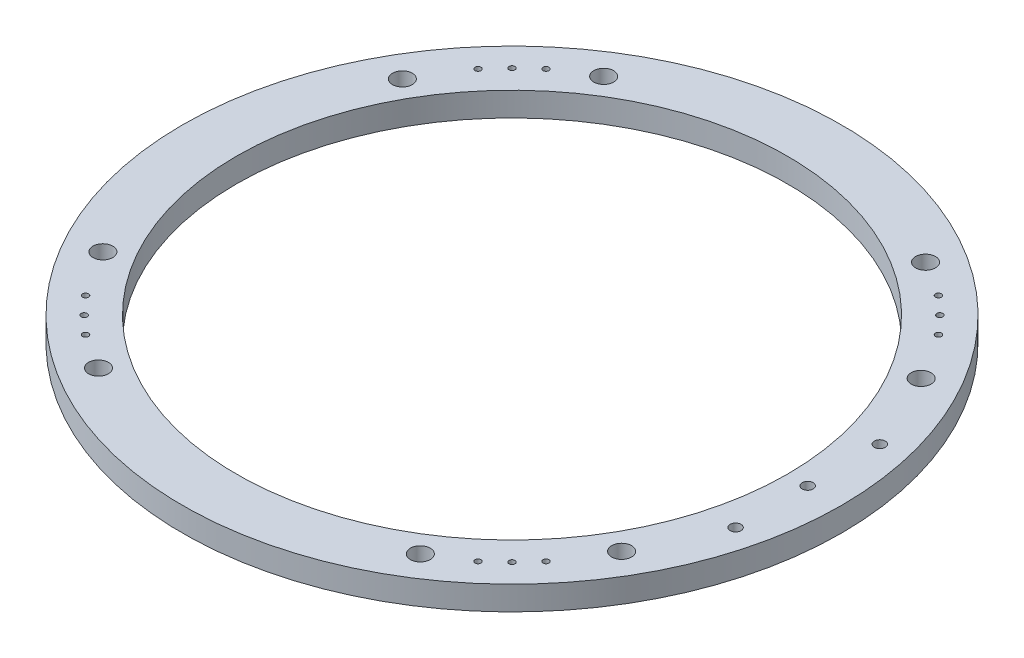
SolidWorks part; units mm, degrees
material "Oak"
ref_plane "Front Plane" through (0, 0, 0) normal (0, 0, 1) x (1, 0, 0)
ref_plane "Top Plane" through (0, 0, 0) normal (0, 1, 0) x (1, 0, 0)
ref_plane "Right Plane" through (0, 0, 0) normal (1, 0, 0) x (0, 0, -1)
sketch "Sketch1" plane through (0, 0, 0) normal (0, 0, 1) x (1, 0, 0)
  line L0 (0, 1125.8152) -> (0, -48874.1848) construction
  line L1 (145.5262, 1052.195) -> (152.4, 1052.195)
  line L9 (145.5262, 1064.895) -> (174.1012, 1064.895)
  line L10 (145.5262, 1064.895) -> (145.5262, 1052.195)
  line L11 (145.5262, 1052.195) -> (174.1012, 1052.195)
  line L12 (174.1012, 1064.895) -> (174.1012, 1052.195)
revolve "Revolve1" add sketch "Sketch1" angle 360 about L0 region at (159.8137, 1058.545, 0)
hole_wizard "9/32 (0.28125) Diameter Hole1" positions "Sketch9" profile "Sketch10" hole size "9/32" standard "ANSI Inch" end condition through all
sketch "Sketch9" plane through (0, 1052.195, 0) normal (0, -1, 0) x (-1, 0, 0)
  line L0 (0, 0) -> (113.0054, 113.0054) construction
  line L3 (0, 0) -> (103.6677, 121.6282) construction
  arc A0 (103.6677, 121.6282) -> (121.6282, 103.6677) centre (0, 0) cw
  circle A1 centre (0, 0) radius 159.8137 construction
  point P0 (103.6677, 121.6282)
  point P2 (121.6282, 103.6677)
  point P15 (113.0054, 113.0054)
sketch "Sketch10" plane through (-103.6677, 1052.195, -121.6282) normal (1, 0, 0) x (0, 0, -1)
  line L0 (0, 0) -> (0, 12.7)
  line L1 (0, 12.7) -> (3.5719, 12.7)
  line L2 (3.5719, 12.7) -> (3.5719, 0)
  line L5 (3.5719, 0) -> (0, 0)
  line L11 (0, -6.35) -> (0, 107.95) construction
  dimension "Thru Hole Dia." = 7.1437
  dimension "Thru Hole Depth" = 12.7
pattern_circular "CirPattern1" count 4 over 360 about axis through (0, 1125.8152, 0) along (0, 1, 0) of "9/32 (0.28125) Diameter Hole1"
ref_plane "Plane1" through (0, 1058.545, 0) normal (0, 1, 0) x (1, 0, 0)
hole_wizard "M5 Clearance Hole1" positions "Sketch14" profile "Sketch15" hole size "M5" standard "ANSI Metric" end condition through all
sketch "Sketch14" plane through (0, 1064.895, 0) normal (0, 1, 0) x (1, 0, 0)
  point P9 (156.21, -38.1)
  point P12 (156.21, 0)
  point P14 (156.21, 38.1)
sketch "Sketch15" plane through (156.21, 1064.895, 38.1) normal (1, 0, 0) x (0, 0, 1)
  line L0 (0, 0) -> (0, 12.7)
  line L1 (0, 12.7) -> (2.9, 12.7)
  line L2 (2.9, 12.7) -> (2.9, 0)
  line L5 (2.9, 0) -> (0, 0)
  line L11 (0, -6.35) -> (0, 107.95) construction
  dimension "Thru Hole Dia." = 5.8
  dimension "Thru Hole Depth" = 12.7
hole_wizard "Z (0.413) Diameter Hole1" positions "Sketch16" profile "Sketch17" hole size "Z" standard "ANSI Inch" end condition through all
sketch "Sketch16" plane through (0, 1064.895, 0) normal (0, 1, 0) x (1, 0, 0)
  line L0 (-137.0279, -79.1131) -> (137.0279, 79.1131) construction
  line L4 (137.0279, -79.1131) -> (-137.0279, 79.1131) construction
  line L6 (0, 0) -> (0, 158.2262) construction
  line L8 (-85.0149, -133.4467) -> (85.0149, 133.4467) construction
  line L11 (-85.0149, 133.4467) -> (85.0149, -133.4467) construction
  circle A0 centre (0, 0) radius 158.2262 construction
  circle A1 centre (0, 0) radius 145.5262 construction
  point P0 (-137.0279, -79.1131)
  point P2 (137.0279, -79.1131)
  point P4 (137.0279, 79.1131)
  point P6 (-137.0279, 79.1131)
  point P37 (-85.0149, 133.4467)
  point P39 (85.0149, 133.4467)
  point P41 (85.0149, -133.4467)
  point P43 (-85.0149, -133.4467)
  dimension "D2" = 12.7
  dimension "D1" = 120
  dimension "D3" = 65
sketch "Sketch17" plane through (-137.0279, 1064.895, 79.1131) normal (1, 0, 0) x (0, 0, 1)
  line L0 (0, 0) -> (0, 12.7)
  line L1 (0, 12.7) -> (5.2451, 12.7)
  line L2 (5.2451, 12.7) -> (5.2451, 0)
  line L5 (5.2451, 0) -> (0, 0)
  line L11 (0, -6.35) -> (0, 107.95) construction
  dimension "Thru Hole Dia." = 10.4902
  dimension "Thru Hole Depth" = 12.7
sketch "Sketch18" plane through (0, 1064.895, 0) normal (0, 1, 0) x (1, 0, 0)
  circle A5 centre (-103.6677, 121.6282) radius 1.5875
  circle A6 centre (-113.0054, 113.0054) radius 1.5875
  circle A7 centre (-121.6282, 103.6677) radius 1.5875
  circle A10 centre (103.6677, 121.6282) radius 1.5875
  circle A11 centre (113.0054, 113.0054) radius 1.5875
  circle A12 centre (121.6282, 103.6677) radius 1.5875
  circle A14 centre (-121.6282, -103.6677) radius 1.5875
  circle A37 centre (-113.0054, -113.0054) radius 1.5875
  circle A38 centre (-103.6677, -121.6282) radius 1.5875
  circle A39 centre (103.6677, -121.6282) radius 1.5875
  circle A40 centre (113.0054, -113.0054) radius 1.5875
  circle A41 centre (121.6282, -103.6677) radius 1.5875
  circle A53 centre (103.6677, 121.6282) radius 3.5719
  circle A54 centre (103.6677, 121.6282) radius 3.5719
  circle A55 centre (113.0054, 113.0054) radius 3.5719
  circle A56 centre (113.0054, 113.0054) radius 3.5719
  circle A57 centre (103.6677, -121.6282) radius 3.5719
  circle A58 centre (103.6677, -121.6282) radius 3.5719
  circle A59 centre (-121.6282, -103.6677) radius 3.5719
  circle A60 centre (-121.6282, -103.6677) radius 3.5719
  circle A61 centre (-103.6677, -121.6282) radius 3.5719
  circle A62 centre (-103.6677, -121.6282) radius 3.5719
  circle A63 centre (-113.0054, -113.0054) radius 3.5719
  circle A64 centre (-113.0054, -113.0054) radius 3.5719
  circle A65 centre (-103.6677, 121.6282) radius 3.5719
  circle A66 centre (-103.6677, 121.6282) radius 3.5719
  circle A67 centre (-121.6282, 103.6677) radius 3.5719
  circle A68 centre (-121.6282, 103.6677) radius 3.5719
  circle A69 centre (-113.0054, 113.0054) radius 3.5719
  circle A70 centre (-113.0054, 113.0054) radius 3.5719
  circle A73 centre (113.0054, -113.0054) radius 3.5719
  circle A74 centre (113.0054, -113.0054) radius 3.5719
  circle A75 centre (121.6282, -103.6677) radius 3.5719
  circle A76 centre (121.6282, -103.6677) radius 3.5719
  circle A77 centre (121.6282, 103.6677) radius 3.5719
  circle A78 centre (121.6282, 103.6677) radius 3.5719
  point P0 (121.6282, 103.2086)
  point P2 (-121.6282, 103.0636)
  point P3 (0, 0)
  point P4 (-103.6677, 122.1461)
  point P5 (-113.6286, -113.0054)
  point P7 (-113.0054, 113.5542)
  point P8 (-121.6282, -104.1526)
  point P10 (-103.1552, -121.6282)
  point P11 (103.6677, -121.8151)
  point P13 (113.21, -113.0054)
  point P14 (121.8485, -103.9119)
  point P16 (0, 0)
  dimension "D13" = 3.175
  dimension "D14" = 0
  dimension "D15" = 0
  dimension "D16" = 0
  dimension "D17" = 0
  dimension "D18" = 0
  dimension "D19" = 0
  dimension "D20" = 0
  dimension "D21" = 0
  dimension "D22" = 0
  dimension "D24" = 0
  dimension "D25" = 0
  dimension "D26" = 0
extrude "Boss-Extrude1" add sketch "Sketch18" against normal up to surface (12.7 mm away) up to face at (-137.0279, 1052.195, 84.3582)
